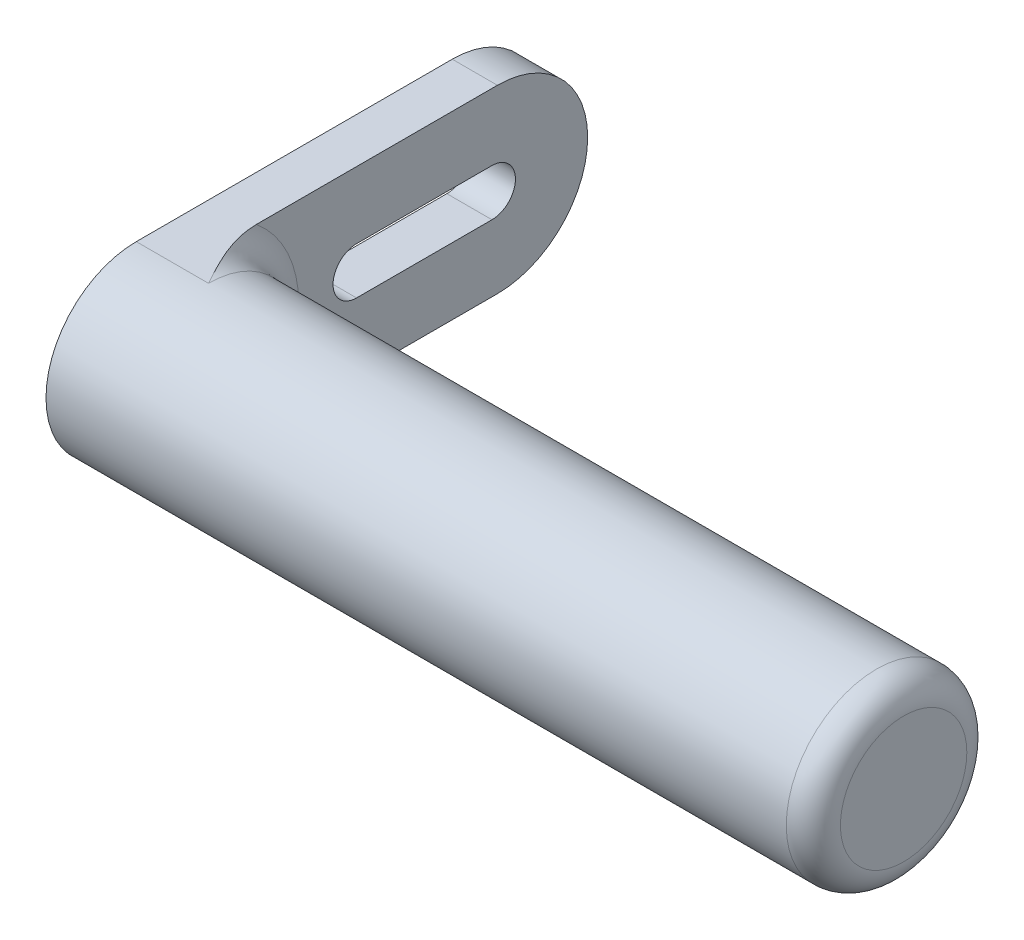
SolidWorks part; units mm, degrees
ref_plane "Front Plane" through (0, 0, 0) normal (0, 0, 1) x (1, 0, 0)
ref_plane "Top Plane" through (0, 0, 0) normal (0, 1, 0) x (1, 0, 0)
ref_plane "Right Plane" through (0, 0, 0) normal (1, 0, 0) x (0, 0, -1)
sketch "Sketch1" plane through (0, 0, 0) normal (1, 0, 0) x (0, 0, -1)
  line L1 (27.5, -10) -> (-27.5, -10)
  line L2 (27.5, -10) -> (27.5, 10)
  line L3 (27.5, 10) -> (-27.5, 10)
  line L4 (-27.5, -10) -> (-27.5, 10)
  line L5 (27.5, -10) -> (-27.5, 10) construction
  line L6 (27.5, 10) -> (-27.5, -10) construction
  point P0 (0, 0)
  dimension "D1" = 20
  dimension "D2" = 55
extrude "Boss-Extrude1" add sketch "Sketch1" along normal blind 5
fillet "Fillet1" radius 10 4 edges at (2.5, -10, -27.5) (2.5, 10, -27.5) (2.5, -10, 27.5) (2.5, 10, 27.5)
sketch "Sketch2" plane through (5, 0, 0) normal (1, 0, 0) x (0, 0, -1)
  line L1 (16.9, 2.6) -> (1.9, 2.6)
  line L3 (16.9, -2.6) -> (1.9, -2.6)
  arc A0 (16.9, 2.6) -> (16.9, -2.6) centre (16.9, 0) cw
  arc A1 (1.9, 2.6) -> (1.9, -2.6) centre (1.9, 0) ccw
  point P7 (19.5, 0)
  point P8 (17.5, 0)
  dimension "D3" = 8
  dimension "D1" = 5.2
  dimension "D2" = 15
extrude "Cut-Extrude1" cut sketch "Sketch2" against normal through all
sketch "Sketch4" plane through (5, 0, 0) normal (1, 0, 0) x (0, 0, -1)
  circle A1 centre (-17.5, 0) radius 10
  dimension "D1" = 20
extrude "Boss-Extrude2" add sketch "Sketch4" along normal blind 80
fillet "Fillet2" radius 3 1 edges at (5, 0, 7.5)
fillet "Fillet3" radius 3 1 edges at (85, 0, 7.5)
